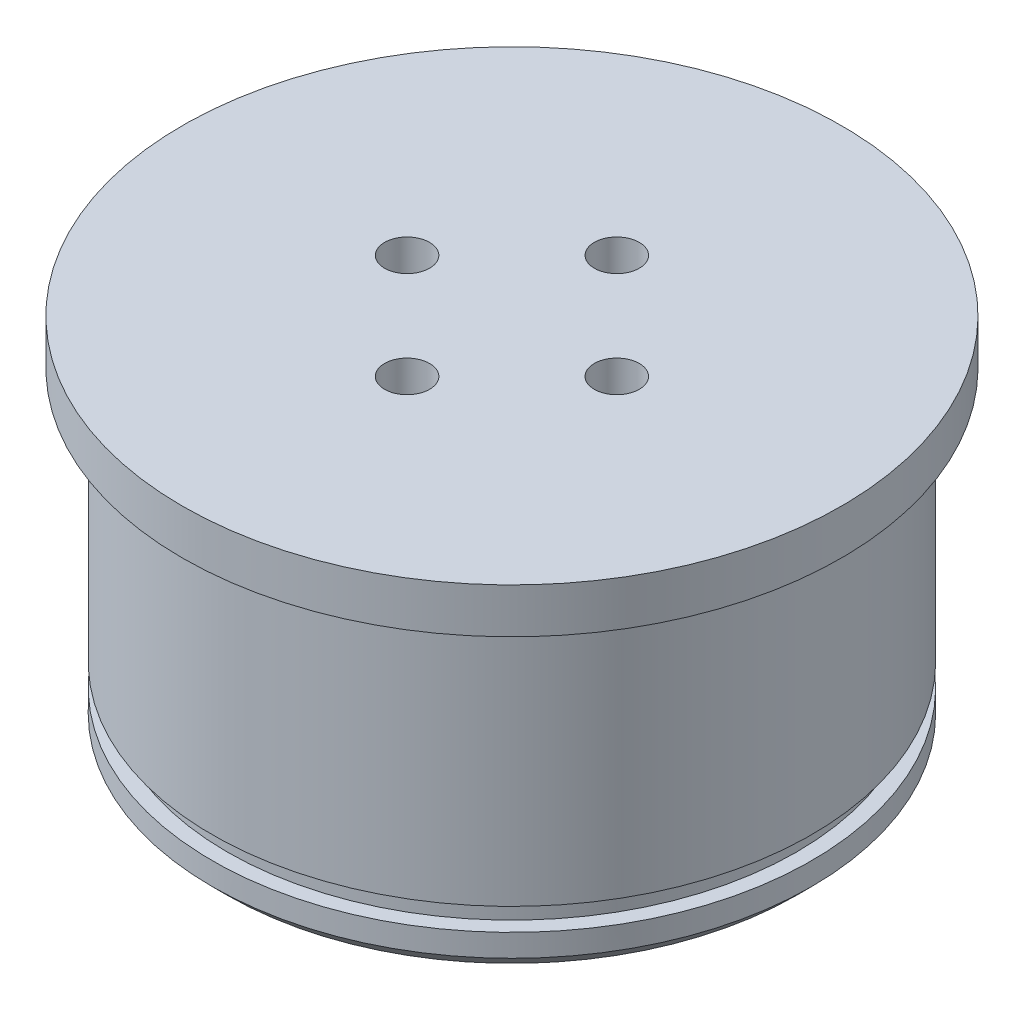
SolidWorks part; units mm, degrees
ref_plane "Спереди" through (0, 0, 0) normal (0, 0, 1) x (1, 0, 0)
ref_plane "Сверху" through (0, 0, 0) normal (0, 1, 0) x (1, 0, 0)
ref_plane "Справа" through (0, 0, 0) normal (1, 0, 0) x (0, 0, -1)
sketch "Эскиз1" plane through (0, 0, 0) normal (0, 1, 0) x (1, 0, 0)
  circle A0 centre (0, 0) radius 20
  dimension "D1" = 40
extrude "Бобышка-Вытянуть1" add sketch "Эскиз1" along normal blind 21
sketch "Эскиз2" plane through (0, 0, 0) normal (0, -1, 0) x (1, 0, 0)
  circle A0 centre (0, 0) radius 10
  dimension "D1" = 20
extrude "Вырез-Вытянуть2" cut sketch "Эскиз2" against normal blind 2.5
ref_plane "Плоскость1" through (0, 2.5, 0) normal (0, -1, 0) x (-1, 0, 0)
sketch "Эскиз5" plane through (0, 2.5, 0) normal (0, -1, 0) x (-1, 0, 0)
  circle A0 centre (0, 0) radius 19
  circle A1 centre (0, 0) radius 20
  dimension "D1" = 38
  dimension "D2" = 40
extrude "Вырез-Вытянуть5" cut sketch "Эскиз5" against normal blind 1.5
chamfer "Фаска1" distance 1 angle 45 1 edges at (0, 0, 20)
sketch "Эскиз6" plane through (0, 21, 0) normal (0, 1, 0) x (1, 0, 0)
  circle A0 centre (0, 0) radius 22
  dimension "D1" = 44
extrude "Бобышка-Вытянуть2" add sketch "Эскиз6" along normal blind 3
sketch "Эскиз4" plane through (0, 2.5, 0) normal (0, -1, 0) x (1, 0, 0)
  circle A0 centre (0, 7) radius 1.5
  dimension "D2" = 3
  dimension "D1" = 7
extrude "Вырез-Вытянуть6" cut sketch "Эскиз4" against normal through all
pattern_circular "Круговой массив1" count 4 over 360 about axis through (0, 2.5, 0) along (0, -1, 0) of "Вырез-Вытянуть6" reverse direction yes
